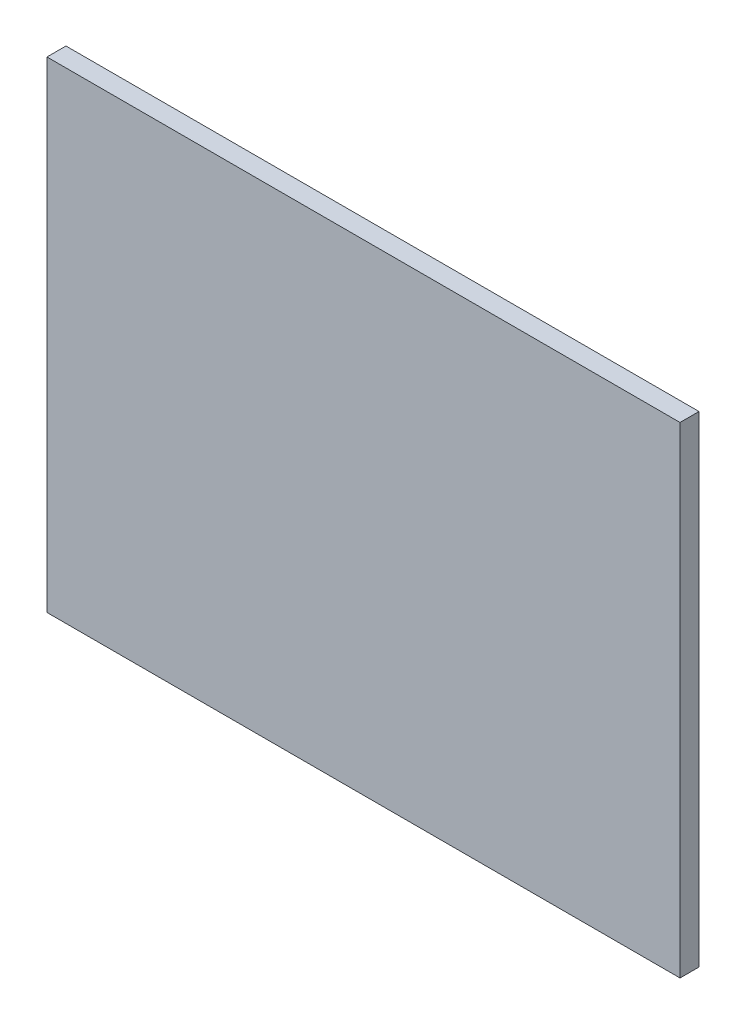
SolidWorks part; units mm, degrees
ref_plane "Plan de face" through (0, 0, 0) normal (0, 0, 1) x (1, 0, 0)
ref_plane "Plan de dessus" through (0, 0, 0) normal (0, 1, 0) x (1, 0, 0)
ref_plane "Plan de droite" through (0, 0, 0) normal (1, 0, 0) x (0, 0, -1)
sketch "Esquisse1" plane through (0, 0, 0) normal (0, 0, 1) x (1, 0, 0)
  line L1 (0, 0) -> (100, 0)
  line L2 (0, 0) -> (0, 76)
  line L3 (0, 76) -> (100, 76)
  line L4 (100, 0) -> (100, 76)
extrude "Boss.-Extru.1" add sketch "Esquisse1" along normal blind 3
